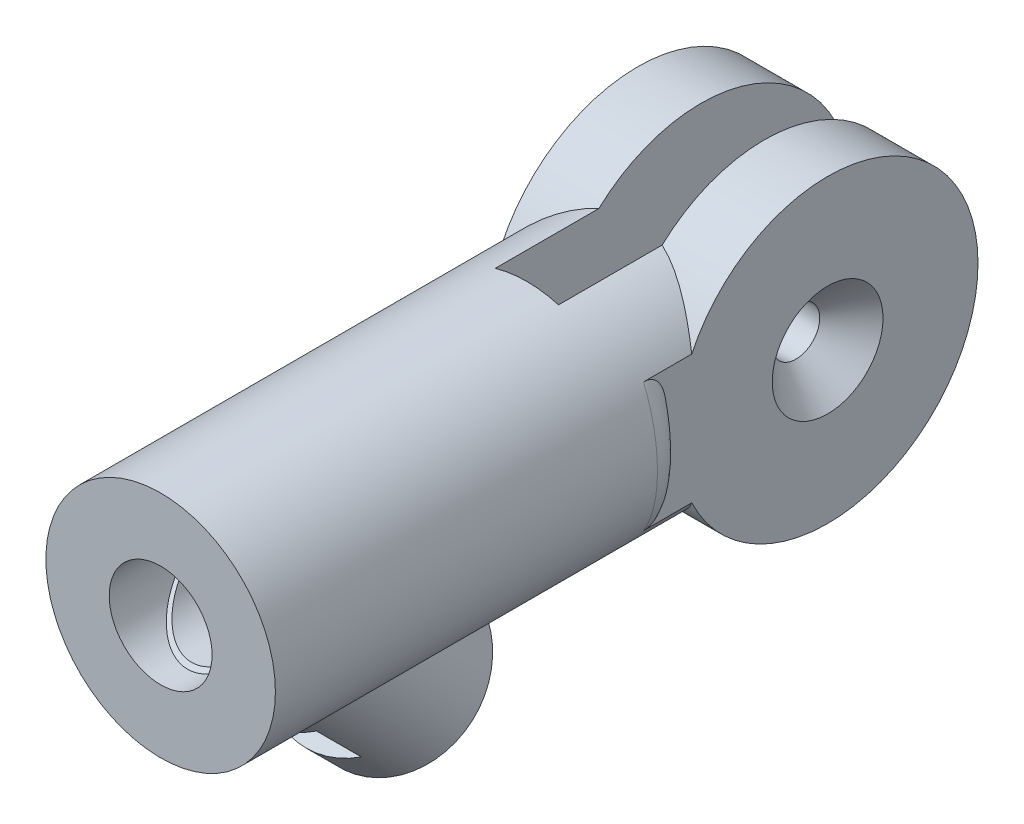
SolidWorks part; units mm, degrees
ref_plane "Спереди" through (0, 0, 0) normal (0, 0, 1) x (1, 0, 0)
ref_plane "Сверху" through (0, 0, 0) normal (0, 1, 0) x (1, 0, 0)
ref_plane "Справа" through (0, 0, 0) normal (1, 0, 0) x (0, 0, -1)
sketch "Sketch1" plane through (0, 0, 0) normal (0, 0, 1) x (1, 0, 0)
  circle A0 centre (0, 0) radius 3.25
  circle A1 centre (0, 0) radius 7.25
  dimension "D1" = 6.5
  dimension "D2" = 4
extrude "Boss-Extrude1" add sketch "Sketch1" along normal blind 30
sketch "Sketch2" plane through (0, 0, 0) normal (1, 0, 0) x (0, 0, -1)
  circle A0 centre (6.139, 0) radius 9.5
  dimension "D1" = 19
extrude "Boss-Extrude2" add sketch "Sketch2" along normal mid plane 12
sketch "Sketch4" plane through (-6, 0, 0) normal (-1, 0, 0) x (0, 0, 1)
  circle A0 centre (-6.139, 0) radius 1.5
  dimension "D1" = 3
extrude "Cut-Extrude1" cut sketch "Sketch4" against normal mid plane 34
sketch "Sketch5" plane through (6, 0, 0) normal (1, 0, 0) x (0, 0, -1)
  circle A0 centre (6.139, 0) radius 10
extrude "Cut-Extrude2" cut sketch "Sketch5" along normal blind 31
sketch "Sketch6" plane through (-6, 0, 0) normal (-1, 0, 0) x (0, 0, 1)
  circle A0 centre (-6.139, 0) radius 10
extrude "Cut-Extrude3" cut sketch "Sketch6" along normal blind 25
fillet "Fillet3" radius 2 2 edges at (7.2499, -0.0454, 3.8609) (-7.2499, 0.0454, 3.8609)
sketch "Sketch7" plane through (0, 0, 0) normal (1, 0, 0) x (0, 0, -1)
  line L1 (19.139, -13) -> (-6.861, -13)
  line L2 (19.139, -13) -> (19.139, 13)
  line L3 (19.139, 13) -> (-6.861, 13)
  line L4 (-6.861, -13) -> (-6.861, 13)
  line L5 (19.139, -13) -> (-6.861, 13) construction
  line L6 (19.139, 13) -> (-6.861, -13) construction
  point P0 (6.139, 0)
  dimension "D1" = 26
extrude "Cut-Extrude4" cut sketch "Sketch7" against normal mid plane 4
sketch "Sketch8" plane through (0, 0, 0) normal (1, 0, 0) x (0, 0, -1)
  line L0 (-33.2006, 0) -> (-12.6296, 0) construction
  line L1 (-25.0463, 0) -> (-12.2665, -12.7799) construction
  line L2 (-25.0463, 0) -> (-28.5819, -3.5355)
  line L3 (-28.5819, -3.5355) -> (-18.6824, -13.435)
  line L4 (-18.6824, -13.435) -> (-15.1468, -9.8995)
  line L5 (-15.1468, -9.8995) -> (-25.0463, 0)
  point P9 (-21.9905, -3)
  point P10 (-24.5284, -0.6557)
  dimension "D1" = 45
  dimension "D2" = 5
  dimension "D3" = 14
revolve "Revolve1" add sketch "Sketch8" angle 360 about L1
sketch "Sketch9" plane through (0, 2.6237, 2.6237) normal (0, -0.7071, -0.7071) x (1, 0, 0)
  circle A0 centre (0, 17.7104) radius 1.5
  dimension "D1" = 3
extrude "Cut-Extrude5" cut sketch "Sketch9" against normal blind 15
sketch "Sketch10" plane through (0, 0, 30) normal (0, 0, 1) x (1, 0, 0)
  circle A0 centre (0, 0) radius 3
  dimension "D1" = 6
extrude "Cut-Extrude6" cut sketch "Sketch10" against normal blind 20
ref_plane "Plane1" through (0, 4.745, 4.745) normal (0, -0.7071, -0.7071) x (-1, 0, 0)
sketch "Sketch11" plane through (0, 4.745, 4.745) normal (0, -0.7071, -0.7071) x (-1, 0, 0)
  line L0 (-2.85, -19.3559) -> (-2.85, -33.9247)
  line L1 (0, -14.4195) -> (-2.85, -16.065)
  line L2 (-2.85, -16.065) -> (-2.85, -19.3559)
  line L3 (-2.85, -19.3559) -> (0, -21.0013)
  line L4 (0, -21.0013) -> (2.85, -19.3559)
  line L5 (2.85, -19.3559) -> (2.85, -16.065)
  line L6 (2.85, -16.065) -> (0, -14.4195)
  line L7 (-2.85, -33.9247) -> (2.85, -33.9247)
  line L8 (2.85, -33.9247) -> (2.85, -19.3559)
  circle A0 centre (0, -17.7104) radius 2.85 construction
  dimension "D1" = 5.7
extrude "Cut-Extrude7" cut sketch "Sketch11" against normal blind 3 contours L7 L8 L4 L3 L0 | L5 L6 L1 L2 L3 L4 region at (0, -14.3776, 23.8676) region at (0, -7.7782, 17.2682)
chamfer "Chamfer1" distance 1 angle 45 1 edges at (0, -9.1924, 22.925)
chamfer "Chamfer2" distance 2 angle 45 2 edges at (-6, 0, -7.639) (6, 0, -7.639)
sketch "Sketch12" plane through (0, 2.6237, 2.6237) normal (0, -0.7071, -0.7071) x (1, 0, 0)
  circle A0 centre (0, 17.7104) radius 5
extrude "Cut-Extrude8" cut sketch "Sketch12" along normal blind 15
